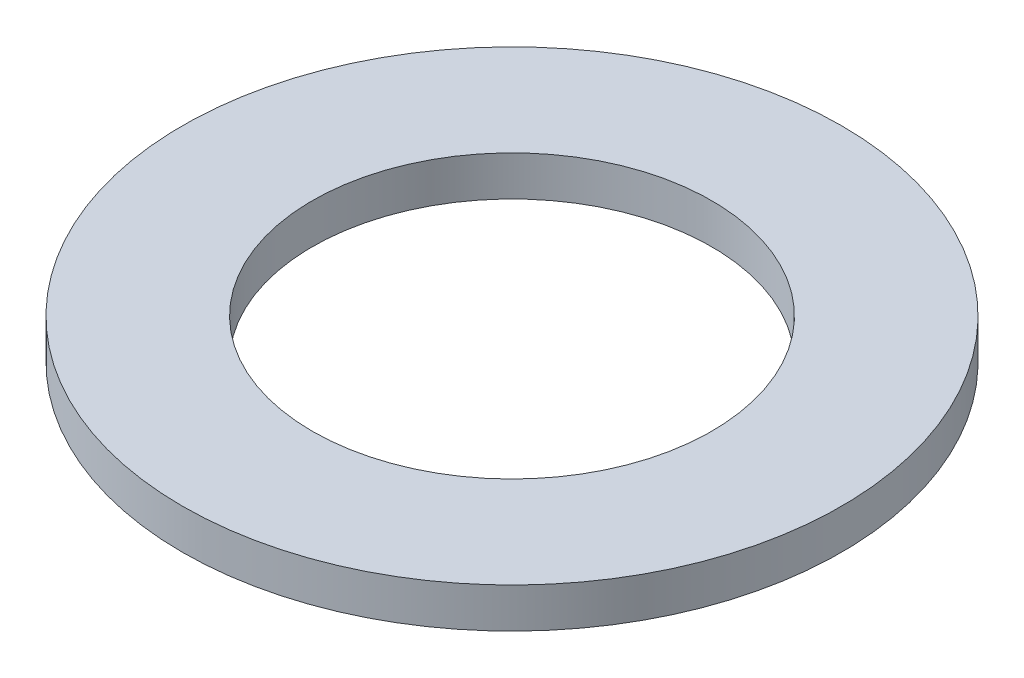
SolidWorks part; units mm, degrees
ref_plane "Front Plane" through (0, 0, 0) normal (0, 0, 1) x (1, 0, 0)
ref_plane "Top Plane" through (0, 0, 0) normal (0, 1, 0) x (1, 0, 0)
ref_plane "Right Plane" through (0, 0, 0) normal (1, 0, 0) x (0, 0, -1)
sketch "Sketch1" plane through (0, 0, 0) normal (0, 1, 0) x (1, 0, 0)
  circle A0 centre (0, 0) radius 82.5
  dimension "FLANGE_OD" = 165
extrude "Boss-Extrude1" add sketch "Sketch1" along normal blind 10
sketch "Sketch2" plane through (0, 0, 0) normal (0, 1, 0) x (1, 0, 0)
  circle A0 centre (0, 0) radius 50
  dimension "BORE_D" = 100
extrude "Cut-Extrude1" cut sketch "Sketch2" along normal through all
sketch "Sketch3" plane through (0, 10, 0) normal (0, 1, 0) x (1, 0, 0)
  circle A0 centre (0, 0) radius 33.6071 construction
  circle A1 centre (-33.6071, 0) radius 1.7368
  dimension "BOLT_D" = 3.4736
  dimension "BOLT_PCD" = 67.2141
extrude "Cut-Extrude2" cut sketch "Sketch3" against normal blind 8.154 rebuild error yes
pattern_circular "CirPattern1" count 8 over 360 rebuild error yes
